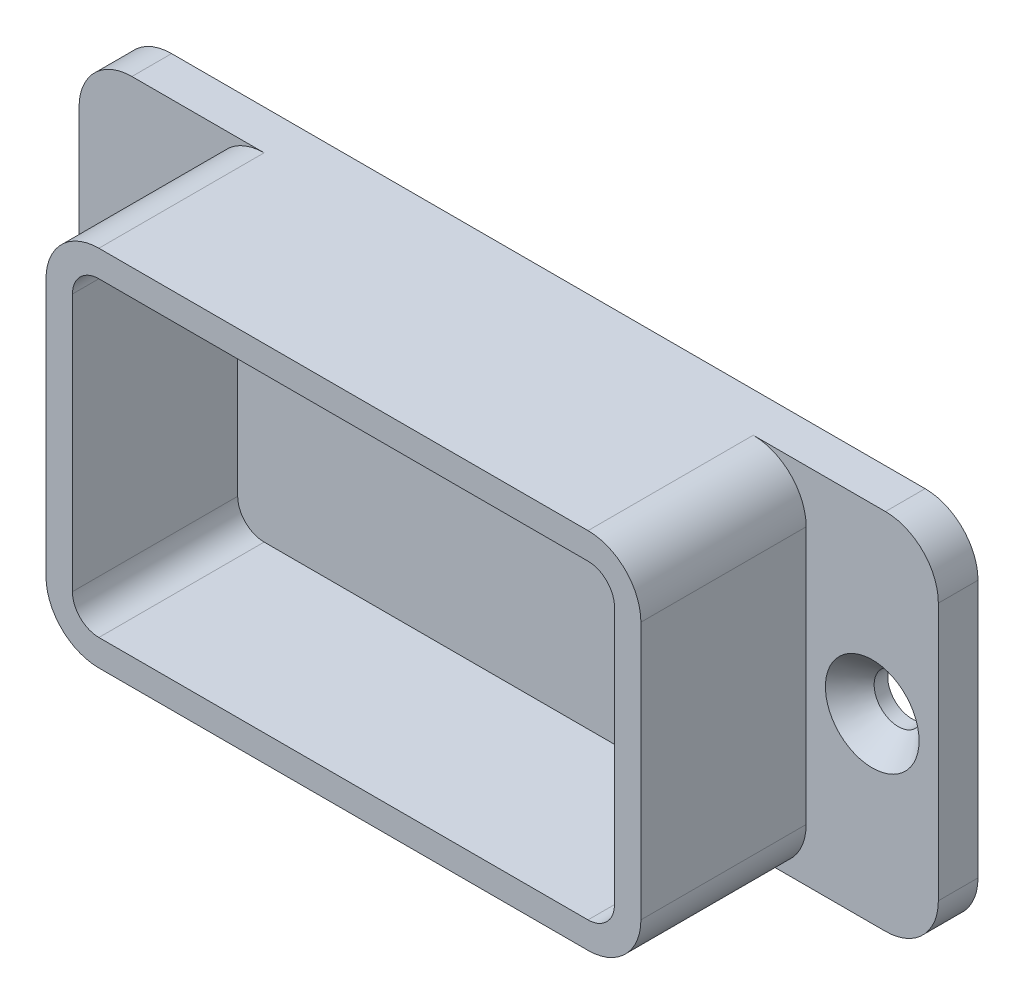
SolidWorks part; units mm, degrees
ref_plane "Front Plane" through (0, 0, 0) normal (0, 0, 1) x (1, 0, 0)
ref_plane "Top Plane" through (0, 0, 0) normal (0, 1, 0) x (1, 0, 0)
ref_plane "Right Plane" through (0, 0, 0) normal (1, 0, 0) x (0, 0, -1)
ref_plane "Bottom Plane" through (0, 0, -2.5) normal (0, 0, 1) x (1, 0, 0)
ref_plane "Top of Walls Plane" through (0, 0, 13) normal (0, 0, 1) x (1, 0, 0)
sketch "Walls Sketch" plane through (0, 0, -2.5) normal (0, 0, 1) x (1, 0, 0)
  line L1 (-20.5, -11.75) -> (20.5, -11.75)
  line L2 (-20.5, -11.75) -> (-20.5, 11.75)
  line L3 (-20.5, 11.75) -> (20.5, 11.75)
  line L4 (20.5, -11.75) -> (20.5, 11.75)
  line L5 (-20.5, -11.75) -> (20.5, 11.75) construction
  line L6 (-20.5, 11.75) -> (20.5, -11.75) construction
  line L7 (-22.5, -13.75) -> (22.5, -13.75)
  line L8 (-22.5, -13.75) -> (-22.5, 13.75)
  line L9 (-22.5, 13.75) -> (22.5, 13.75)
  line L10 (22.5, -13.75) -> (22.5, 13.75)
  line L11 (-22.5, -13.75) -> (22.5, 13.75) construction
  line L12 (-22.5, 13.75) -> (22.5, -13.75) construction
  point P0 (0, 0)
  point P6 (0, 0)
  dimension "D1" = 45
  dimension "D2" = 27.5
extrude "Walls Extrude" add sketch "Walls Sketch" along normal up to surface (15.5 mm away) up to plane "Top of Walls Plane"
sketch "Base Sketch" plane through (0, 0, -2.5) normal (0, 0, 1) x (1, 0, 0)
  line L0 (-22.5, -13.75) -> (22.5, -13.75) construction
  line L1 (-32.5, 13.75) -> (32.5, 13.75)
  line L2 (-32.5, 13.75) -> (-32.5, -13.75)
  line L3 (-32.5, -13.75) -> (32.5, -13.75)
  line L4 (32.5, 13.75) -> (32.5, -13.75)
  line L5 (22.5, 13.75) -> (-22.5, 13.75) construction
  line L6 (-22.5, 13.75) -> (-22.5, -13.75) construction
  line L7 (22.5, -13.75) -> (22.5, 13.75) construction
extrude "Base Extrude" add sketch "Base Sketch" along normal blind 3
hole_wizard "No. 6 Mounting Holes" positions "No. 6 Mounting Holes Position Sketch" profile "No. 6 Mounting Holes Profile Sketch" countersink size "#6" standard "ANSI Inch" end condition through all
sketch "No. 6 Mounting Holes Position Sketch" plane through (0, 0, 0.5) normal (0, 0, 1) x (1, 0, 0)
  line L0 (-32.5, 13.75) -> (-22.5, -13.75) construction
  line L2 (22.5, -13.75) -> (32.5, 13.75) construction
  line L3 (22.5, -13.75) -> (32.5, -13.75) construction
  point P0 (-27.5, 0)
  point P19 (27.5, 0)
sketch "No. 6 Mounting Holes Profile Sketch" plane through (-27.5, 0, 0.5) normal (1, 0, 0) x (0, -1, 0)
  line L0 (0, 0) -> (0, 3)
  line L1 (0, 3) -> (1.8288, 3)
  line L2 (1.8288, 3) -> (1.8288, 1.9723)
  line L3 (1.8288, 1.9723) -> (3.5433, 0)
  line L5 (3.5433, 0) -> (0, 0)
  line L6 (-1.8288, 1.9723) -> (-3.5433, 0) construction
  line L11 (0, -6.35) -> (0, 107.95) construction
  dimension "Thru Hole Dia." = 3.6576
  dimension "Thru Hole Depth" = 3
  dimension "Near C'Sink Dia." = 7.0866
  dimension "Near C'Sink Angle" = 82
fillet "Tab Fillets" radius 4 4 edges at (32.5, 13.75, -1) (32.5, -13.75, -1) (-32.5, 13.75, -1) (-32.5, -13.75, -1)
fillet "Inside Corner Fillets" radius 2 4 edges at (-20.5, -11.75, 6.75) (20.5, -11.75, 6.75) (20.5, 11.75, 6.75) (-20.5, 11.75, 6.75)
fillet "Outside Corner Fillets" radius 4 4 edges at (-22.5, 13.75, 6.75) (22.5, 13.75, 6.75) (22.5, -13.75, 6.75) (-22.5, -13.75, 6.75)
